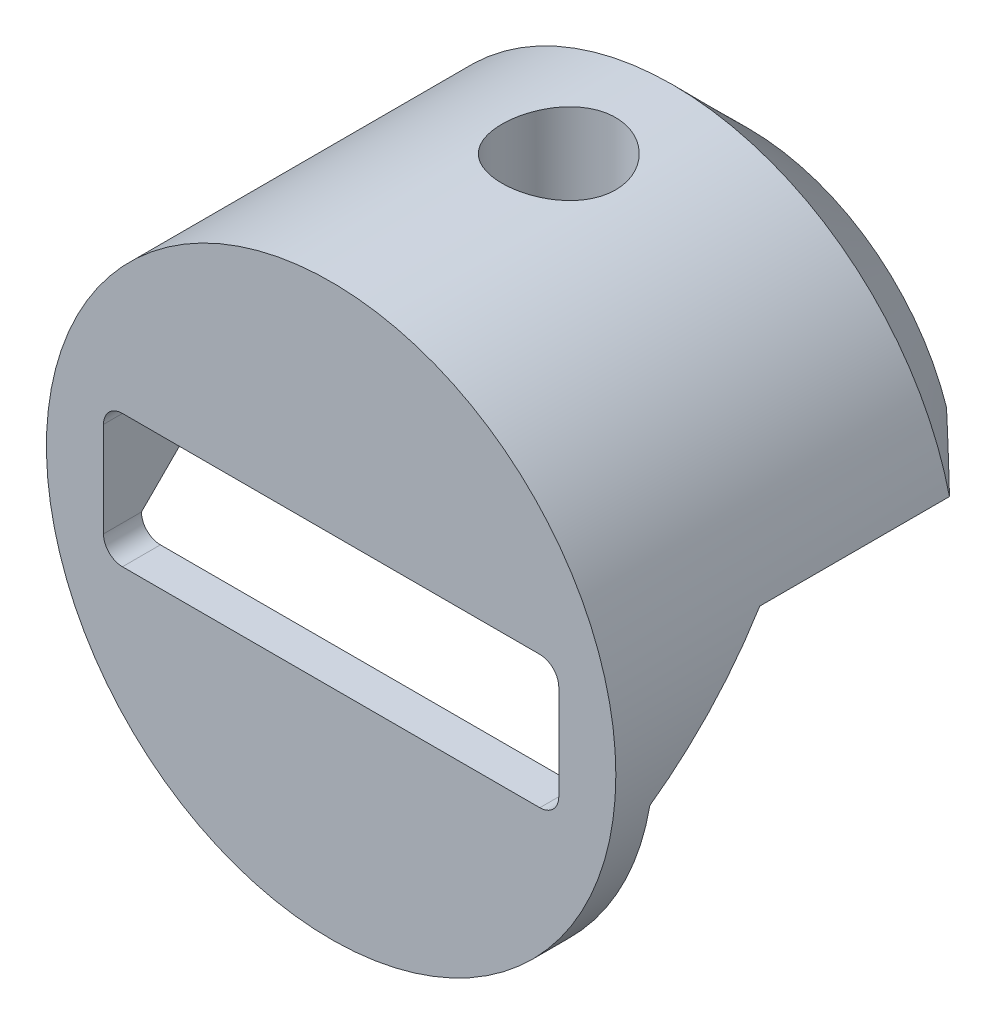
SolidWorks part; units mm, degrees
material "Acrylic (Medium-high impact)"
ref_plane "Front Plane" through (0, 0, 0) normal (0, 0, 1) x (1, 0, 0)
ref_plane "Top Plane" through (0, 0, 0) normal (0, 1, 0) x (1, 0, 0)
ref_plane "Right Plane" through (0, 0, 0) normal (1, 0, 0) x (0, 0, -1)
sketch "Sketch1" plane through (0, 0, 0) normal (0, 0, 1) x (1, 0, 0)
  circle A0 centre (0, 0) radius 23.8252
  dimension "D1" = 47.6504
extrude "Boss-Extrude1" add sketch "Sketch1" along normal blind 3.175
sketch "Sketch8" plane through (0, 0, 3.175) normal (0, 0, 1) x (1, 0, 0)
  line L1 (-19.05, -5.5562) -> (19.05, -5.5562)
  line L2 (-19.05, -5.5562) -> (-19.05, 5.5562)
  line L3 (-19.05, 5.5562) -> (19.05, 5.5562)
  line L4 (19.05, -5.5562) -> (19.05, 5.5562)
  line L5 (-19.05, -5.5562) -> (19.05, 5.5562) construction
  line L6 (-19.05, 5.5562) -> (19.05, -5.5562) construction
  point P0 (0, 0)
  dimension "D1" = 11.1125
  dimension "D2" = 38.1
extrude "Cut-Extrude1" cut sketch "Sketch8" against normal through all
fillet "Fillet1" radius 1.5875 4 edges at (-19.05, -5.5562, 1.5875) (19.05, -5.5562, 1.5875) (19.05, 5.5562, 1.5875) (-19.05, 5.5562, 1.5875)
sketch "Sketch9" plane through (0, 0, 0) normal (0, 0, -1) x (-1, 0, 0)
  line L0 (-17.4625, 5.5562) -> (17.4625, 5.5562) construction
  line L1 (-23.1683, 5.5562) -> (23.1683, 5.5562)
  circle A0 centre (0, 0) radius 23.8252 construction
  arc A1 (23.1683, 5.5562) -> (-23.1683, 5.5562) centre (0, 0) ccw
extrude "Boss-Extrude2" add sketch "Sketch9" along normal blind 31.75 contours L1 A1
chamfer "Chamfer1" distance 9.525 angle 45 2 edges at (20.3154, 5.5562, 0) (-20.3154, 5.5562, 0)
ref_plane "Plane1" through (0, 23.8252, 0) normal (0, 1, 0) x (1, 0, 0)
hole_wizard "CBORE for #8 Binding Head Machine Screw1" positions "Sketch13" profile "Sketch14" counterbore size "#8" standard "ANSI Inch" end condition through all
sketch "Sketch13" plane through (0, 23.8252, 0) normal (0, 1, 0) x (1, 0, 0)
  circle A0 centre (0, 15.875) radius 2.2479 construction
  point P0 (0, 15.875)
sketch "Sketch14" plane through (0, 23.8252, -15.875) normal (1, 0, 0) x (0, 0, 1)
  line L0 (0, 0) -> (0, 47.6504)
  line L1 (0, 47.6504) -> (2.2479, 47.6504)
  line L3 (2.2479, 47.6504) -> (2.2479, 15.367)
  line L4 (2.2479, 15.367) -> (4.7625, 15.367)
  line L5 (4.7625, 15.367) -> (4.7625, 0)
  line L7 (4.7625, 0) -> (0, 0)
  line L11 (0, -6.35) -> (0, 107.95) construction
  dimension "Thru Hole Dia." = 4.4958
  dimension "Thru Hole Depth" = 47.6504
  dimension "C'Bore Dia." = 9.525
  dimension "C'Bore Depth" = 15.367
chamfer "Chamfer3" distance 6.35 angle 45 1 edges at (0, 23.8252, -31.75)
